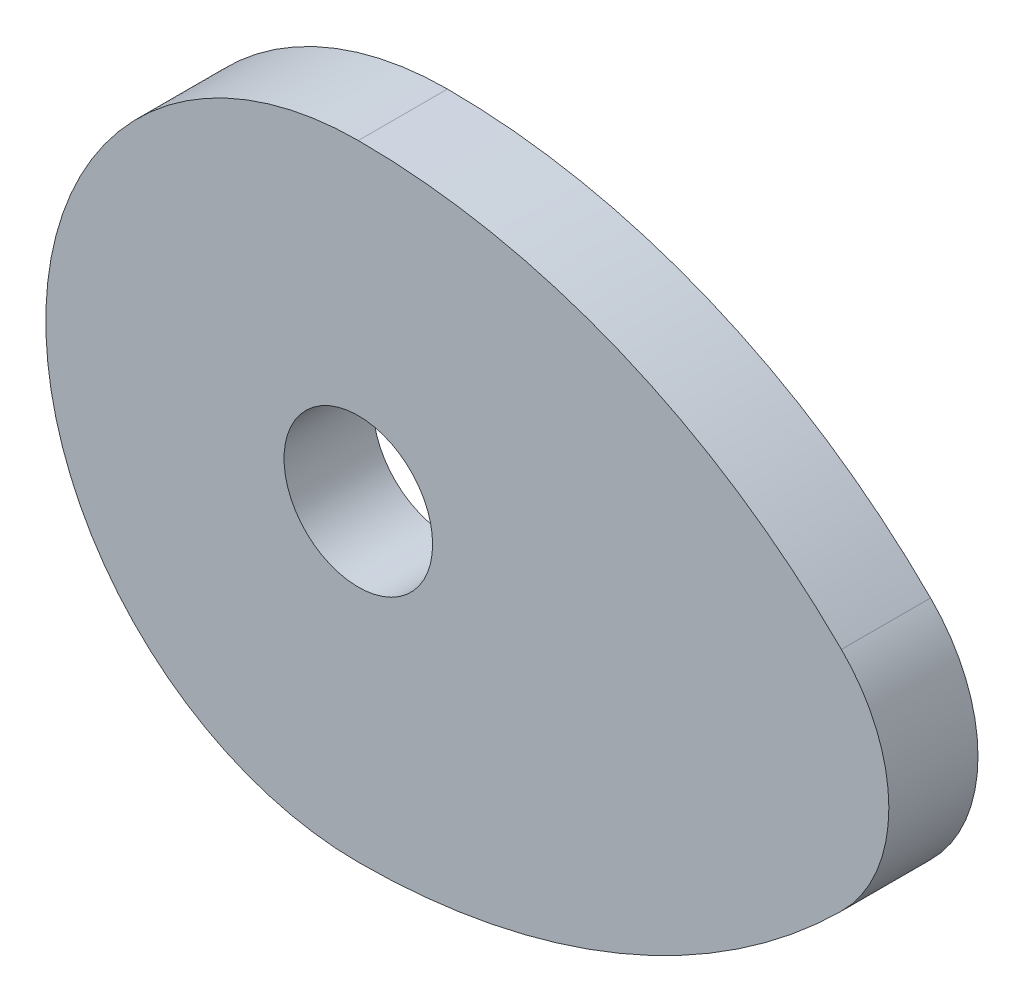
SolidWorks part; units mm, degrees
ref_plane "Front Plane" through (0, 0, 0) normal (0, 0, 1) x (1, 0, 0)
ref_plane "Top Plane" through (0, 0, 0) normal (0, 1, 0) x (1, 0, 0)
ref_plane "Right Plane" through (0, 0, 0) normal (1, 0, 0) x (0, 0, -1)
sketch "Sketch1" plane through (0, 0, 0) normal (0, 0, 1) x (1, 0, 0)
  arc A0 (0, 21.0346) -> (0, -21.0346) centre (0, 0) ccw
  arc A2 (0, 21.0346) -> (32.5135, 7.6277) centre (0, -25.0936) cw
  arc A3 (0, -21.0346) -> (32.5135, -7.6277) centre (0, 25.0936) ccw
  arc A4 (32.5135, -7.6277) -> (32.5135, 7.6277) centre (25, 0) ccw
  circle A5 centre (0, 0) radius 5
extrude "Boss-Extrude3" add sketch "Sketch1" along normal blind 6 contours A0 A3 A4 A2 | A5
ref_axis "Axis4" through (0, 0, 6) along (0, 0, -1)
